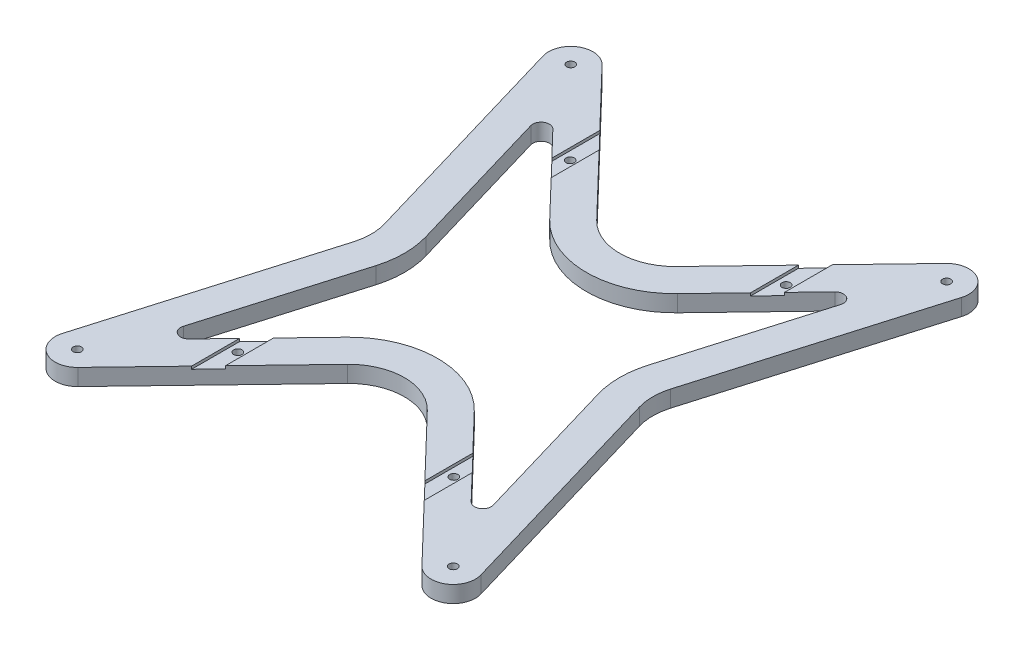
SolidWorks part; units mm, degrees
material "1060 Alloy"
ref_plane "Front Plane" through (0, 0, 0) normal (0, 0, 1) x (1, 0, 0)
ref_plane "Top Plane" through (0, 0, 0) normal (0, 1, 0) x (1, 0, 0)
ref_plane "Right Plane" through (0, 0, 0) normal (1, 0, 0) x (0, 0, -1)
sketch "Sketch1" plane through (0, 0, 0) normal (0, 1, 0) x (1, 0, 0)
  line L0 (-62.1139, 94.6385) -> (0, 30)
  line L1 (0, 30) -> (62.1139, 94.6385)
  line L2 (75.5568, 86.8368) -> (50, 0)
  line L3 (50, 0) -> (75.5568, -86.8368)
  line L4 (62.1139, -94.6385) -> (0, -30)
  line L5 (0, -30) -> (-62.1139, -94.6385)
  line L6 (-75.5568, -86.8368) -> (-50, 0)
  line L7 (-50, 0) -> (-75.5568, 86.8368)
  line L8 (-78.4889, 78.4889) -> (78.4889, -78.4889) construction
  line L9 (-42, 70) -> (-36, 70) construction
  line L10 (-42, 70) -> (-42, 50) construction
  line L11 (-42, 50) -> (-36, 50) construction
  line L12 (-36, 70) -> (-36, 50) construction
  line L13 (-42, 70) -> (-36, 50) construction
  line L14 (-42, 50) -> (-36, 70) construction
  line L15 (36, 70) -> (42, 70) construction
  line L16 (36, 70) -> (36, 50) construction
  line L17 (36, 50) -> (42, 50) construction
  line L18 (42, 70) -> (42, 50) construction
  line L19 (36, 70) -> (42, 50) construction
  line L20 (36, 50) -> (42, 70) construction
  line L21 (36, -50) -> (42, -50) construction
  line L22 (36, -50) -> (36, -70) construction
  line L23 (36, -70) -> (42, -70) construction
  line L24 (42, -50) -> (42, -70) construction
  line L25 (36, -50) -> (42, -70) construction
  line L26 (36, -70) -> (42, -50) construction
  line L27 (-42, -50) -> (-36, -50) construction
  line L28 (-42, -50) -> (-42, -70) construction
  line L29 (-42, -70) -> (-36, -70) construction
  line L30 (-36, -50) -> (-36, -70) construction
  line L31 (-42, -50) -> (-36, -70) construction
  line L32 (-42, -70) -> (-36, -50) construction
  line L33 (111, 45.9777) -> (45.9777, 111) construction
  line L34 (45.9777, 111) -> (-45.9777, 111) construction
  line L35 (-45.9777, 111) -> (-111, 45.9777) construction
  line L36 (-111, 45.9777) -> (-111, -45.9777) construction
  line L37 (-111, -45.9777) -> (-45.9777, -111) construction
  line L38 (-45.9777, -111) -> (45.9777, -111) construction
  line L39 (45.9777, -111) -> (111, -45.9777) construction
  line L40 (111, -45.9777) -> (111, 45.9777) construction
  line L41 (78.4889, 78.4889) -> (-78.4889, -78.4889) construction
  circle A0 centre (-67.8823, 89.0955) radius 1.5
  circle A1 centre (67.8823, 89.0955) radius 1.5
  circle A2 centre (-67.8823, -89.0955) radius 1.5
  circle A3 centre (67.8823, -89.0955) radius 1.5
  arc A4 (-62.1139, 94.6385) -> (-75.5568, 86.8368) centre (-67.8823, 89.0955) ccw
  arc A5 (62.1139, 94.6385) -> (75.5568, 86.8368) centre (67.8823, 89.0955) cw
  arc A6 (-75.5568, -86.8368) -> (-62.1139, -94.6385) centre (-67.8823, -89.0955) ccw
  arc A7 (75.5568, -86.8368) -> (62.1139, -94.6385) centre (67.8823, -89.0955) cw
  circle A8 centre (0, 0) radius 111 construction
  circle A9 centre (-39, 60) radius 1.5
  circle A10 centre (39, 60) radius 1.5
  circle A11 centre (39, -60) radius 1.5
  circle A12 centre (-39, -60) radius 1.5
  ellipse E0 centre (0, 0) end of major axis (50, 0) minor radius 30 construction
  dimension "D5" = 3
  dimension "D6" = 30
  dimension "D7" = 8
  dimension "D12" = 3
  dimension "D3" = 15
  dimension "D4" = 15
  dimension "D8" = 120
  dimension "D9" = 78
  dimension "D10" = 0
  dimension "D11" = 60
  dimension "D13" = 50
  dimension "D14" = 39
  dimension "D15" = 20
  dimension "D16" = 6
  dimension "D17" = 111
  dimension "D18" = 15
extrude "Boss-Extrude1" add sketch "Sketch1" along normal blind 6
fillet "Fillet1" radius 20 4 edges at (0, 3, -30) (-50, 3, 0) (0, 3, 30) (50, 3, 0)
sketch "Sketch2" plane through (0, 6, 0) normal (0, 1, 0) x (1, 0, 0)
  line L44 (-59.4227, 74.5191) -> (-40.1501, 9.0347)
  line L45 (-40.1501, -9.0347) -> (-59.4227, -74.5191)
  line L46 (-59.4227, -74.5191) -> (-23.0735, -36.6925)
  line L47 (23.0735, -36.6925) -> (59.4227, -74.5191)
  line L48 (59.4227, -74.5191) -> (40.1501, -9.0347)
  line L49 (40.1501, 9.0347) -> (59.4227, 74.5191)
  line L50 (59.4227, 74.5191) -> (23.0735, 36.6925)
  line L51 (-23.0735, 36.6925) -> (-59.4227, 74.5191)
  line L52 (-59.4227, 74.5191) -> (-40.1501, 9.0347)
  line L53 (-40.1501, -9.0347) -> (-59.4227, -74.5191)
  line L54 (-59.4227, -74.5191) -> (-23.0735, -36.6925)
  line L55 (23.0735, -36.6925) -> (59.4227, -74.5191)
  line L56 (59.4227, -74.5191) -> (40.1501, -9.0347)
  line L57 (40.1501, 9.0347) -> (59.4227, 74.5191)
  line L58 (59.4227, 74.5191) -> (23.0735, 36.6925)
  line L59 (-23.0735, 36.6925) -> (-59.4227, 74.5191)
  arc A40 (-40.1501, -9.0347) -> (-40.1501, 9.0347) centre (-70.8482, 0) ccw
  arc A41 (23.0735, -36.6925) -> (-23.0735, -36.6925) centre (0, -58.8648) ccw
  arc A42 (40.1501, 9.0347) -> (40.1501, -9.0347) centre (70.8482, 0) ccw
  arc A43 (-23.0735, 36.6925) -> (23.0735, 36.6925) centre (0, 58.8648) ccw
  arc A44 (-40.1501, -9.0347) -> (-40.1501, 9.0347) centre (-70.8482, 0) ccw
  arc A45 (23.0735, -36.6925) -> (-23.0735, -36.6925) centre (0, -58.8648) ccw
  arc A46 (40.1501, 9.0347) -> (40.1501, -9.0347) centre (70.8482, 0) ccw
  arc A47 (-23.0735, 36.6925) -> (23.0735, 36.6925) centre (0, 58.8648) ccw
  dimension "D1" = 12
extrude "Cut-Extrude1" cut sketch "Sketch2" against normal up to next
sketch "Sketch5" plane through (0, 6, 0) normal (0, 1, 0) x (1, 0, 0)
  line L0 (-41.303, 2.9501) -> (0, -4.6826)
  line L1 (-12.94, -8.43) -> (12.94, -8.43) construction
  line L2 (-12.94, -8.43) -> (-12.94, 8.43) construction
  line L3 (-12.94, 8.43) -> (12.94, 8.43) construction
  line L4 (12.94, -8.43) -> (12.94, 8.43) construction
  line L5 (-12.94, -8.43) -> (12.94, 8.43) construction
  line L6 (-12.94, 8.43) -> (12.94, -8.43) construction
  line L8 (0, -4.6826) -> (41.303, 2.9501)
  line L10 (41.303, 2.9501) -> (42.3933, -2.9501)
  line L11 (42.3933, -2.9501) -> (4, -10.045)
  line L12 (4, -10.045) -> (4, -27.1158)
  line L13 (-4, -27.1158) -> (-4, -10.045)
  line L14 (-4, -10.045) -> (-42.3933, -2.9501)
  line L15 (-42.3933, -2.9501) -> (-41.303, 2.9501)
  line L17 (41.8482, 0) -> (-41.8482, 0) construction
  circle A0 centre (-10.3, -5.83) radius 1.25
  circle A1 centre (10.3, -5.83) radius 1.25
  arc A2 (23.0735, -36.6925) -> (-23.0735, -36.6925) centre (0, -58.8648) ccw construction
  arc A3 (4, -27.1158) -> (-4, -27.1158) centre (0, -58.8648) ccw
  arc A4 (-40.1501, -9.0347) -> (-40.1501, 9.0347) centre (-70.8482, 0) ccw construction
  arc A5 (40.1501, 9.0347) -> (40.1501, -9.0347) centre (70.8482, 0) ccw construction
  circle A6 centre (41.8482, 0) radius 3 construction
  circle A7 centre (-41.8482, 0) radius 3 construction
  point P0 (0, 0)
  dimension "D3" = 2.5
  dimension "D10" = 6
  dimension "D1" = 16.86
  dimension "D2" = 25.88
  dimension "D4" = 20.6
  dimension "D5" = 2.64
  dimension "D6" = 2.6
  dimension "D7" = 6
  dimension "D8" = 3
  dimension "D9" = 8
extrude "Boss-Extrude2" [suppressed] add sketch "Sketch5" against normal up to surface (6 mm away) up to face at (0, 0, 0)
fillet "Fillet2" [suppressed] radius 3
sketch "Sketch6" plane through (0, 6, 0) normal (0, 1, 0) x (1, 0, 0)
  line L0 (-14.421, 45.0071) -> (-62.1139, 94.6385) construction
  line L1 (-42, -50.1444) -> (-36, -50.1444)
  line L2 (-42, -50.1444) -> (-42, -73.7071)
  line L3 (-42, -73.7071) -> (-36, -73.7071)
  line L4 (-36, -50.1444) -> (-36, -73.7071)
  line L5 (36, -50.1444) -> (42, -50.1444)
  line L6 (36, -50.1444) -> (36, -73.7071)
  line L7 (36, -73.7071) -> (42, -73.7071)
  line L8 (42, -50.1444) -> (42, -73.7071)
  line L9 (36, 50.1444) -> (42, 50.1444)
  line L10 (36, 50.1444) -> (36, 73.7071)
  line L11 (36, 73.7071) -> (42, 73.7071)
  line L12 (42, 50.1444) -> (42, 73.7071)
  line L13 (-42, 50.1444) -> (-36, 50.1444)
  line L14 (-42, 50.1444) -> (-42, 73.7071)
  line L15 (-42, 73.7071) -> (-36, 73.7071)
  line L16 (-36, 50.1444) -> (-36, 73.7071)
  line L17 (62.1139, 94.6385) -> (14.421, 45.0071) construction
  line L18 (14.421, -45.0071) -> (62.1139, -94.6385) construction
  line L19 (-62.1139, -94.6385) -> (-14.421, -45.0071) construction
  line L20 (-23.0735, 36.6925) -> (-59.4227, 74.5191) construction
  line L21 (-59.4227, -74.5191) -> (-23.0735, -36.6925) construction
  circle A0 centre (-39, -60) radius 1.5 construction
  circle A1 centre (39, -60) radius 1.5 construction
  dimension "D2" = 3
  dimension "D3" = 3
  dimension "D1" = 6
extrude "Cut-Extrude2" cut sketch "Sketch6" against normal blind 1
fillet "Fillet3" radius 3 4 edges at (59.4227, 3, 74.5191) (-59.4227, 3, 74.5191) (59.4227, 3, -74.5191) (-59.4227, 3, -74.5191)
equation "\"D14@Sketch1\"=\"D9@Sketch1\"/2"
